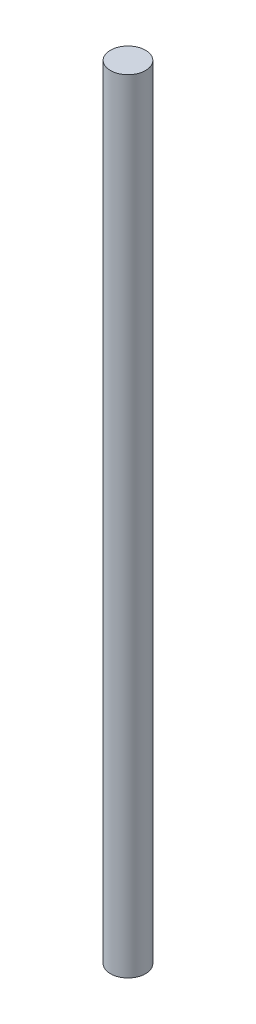
SolidWorks part; units mm, degrees
ref_plane "Front Plane" through (0, 0, 0) normal (0, 0, 1) x (1, 0, 0)
ref_plane "Top Plane" through (0, 0, 0) normal (0, 1, 0) x (1, 0, 0)
ref_plane "Right Plane" through (0, 0, 0) normal (1, 0, 0) x (0, 0, -1)
sketch "Sketch1" plane through (0, 0, 0) normal (0, 1, 0) x (1, 0, 0)
  circle A0 centre (0, 0) radius 1
extrude "Boss-Extrude1" add sketch "Sketch1" along normal blind 44.5
